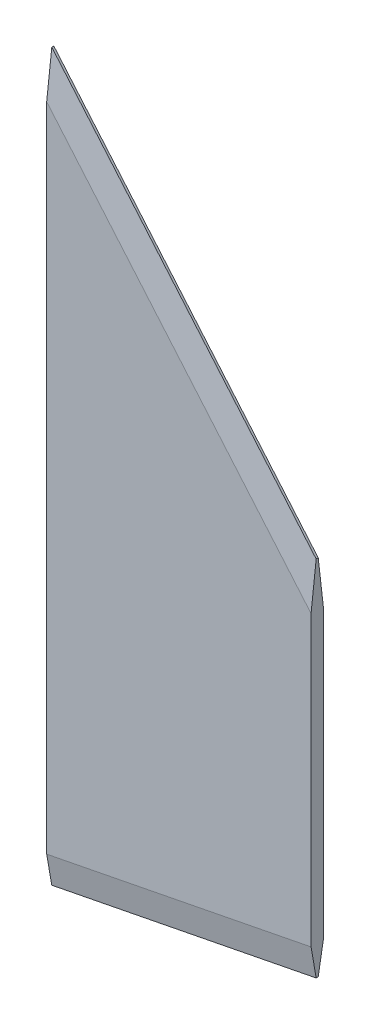
SolidWorks part; units mm, degrees
material "Hexcel AS4C (3000 Filaments)"
ref_plane "Front Plane" through (0, 0, 0) normal (0, 0, 1) x (1, 0, 0)
ref_plane "Top Plane" through (0, 0, 0) normal (0, 1, 0) x (1, 0, 0)
ref_plane "Right Plane" through (0, 0, 0) normal (1, 0, 0) x (0, 0, -1)
sketch "Sketch1" plane through (0, 0, 0) normal (0, 0, 1) x (1, 0, 0)
  line L0 (-60.9816, 77.1065) -> (-60.9816, -100.6935)
  line L1 (-60.9816, -100.6935) -> (3.7884, -87.9935)
  line L2 (3.7884, -87.9935) -> (3.7884, 0.9065)
  line L3 (3.7884, 0.9065) -> (-60.9816, 77.1065)
extrude "Boss-Extrude1" add sketch "Sketch1" along normal mid plane 3
chamfer "Chamfer1" distance 1.25 angle 80 4 edges at (-28.5966, -94.3435, -1.5) (-28.5966, -94.3435, 1.5) (-28.5966, 39.0065, -1.5) (-28.5966, 39.0065, 1.5) first distance on face at (-28.5966, -94.3435, 0) first distance on face at (-28.5966, 39.0065, 0)
